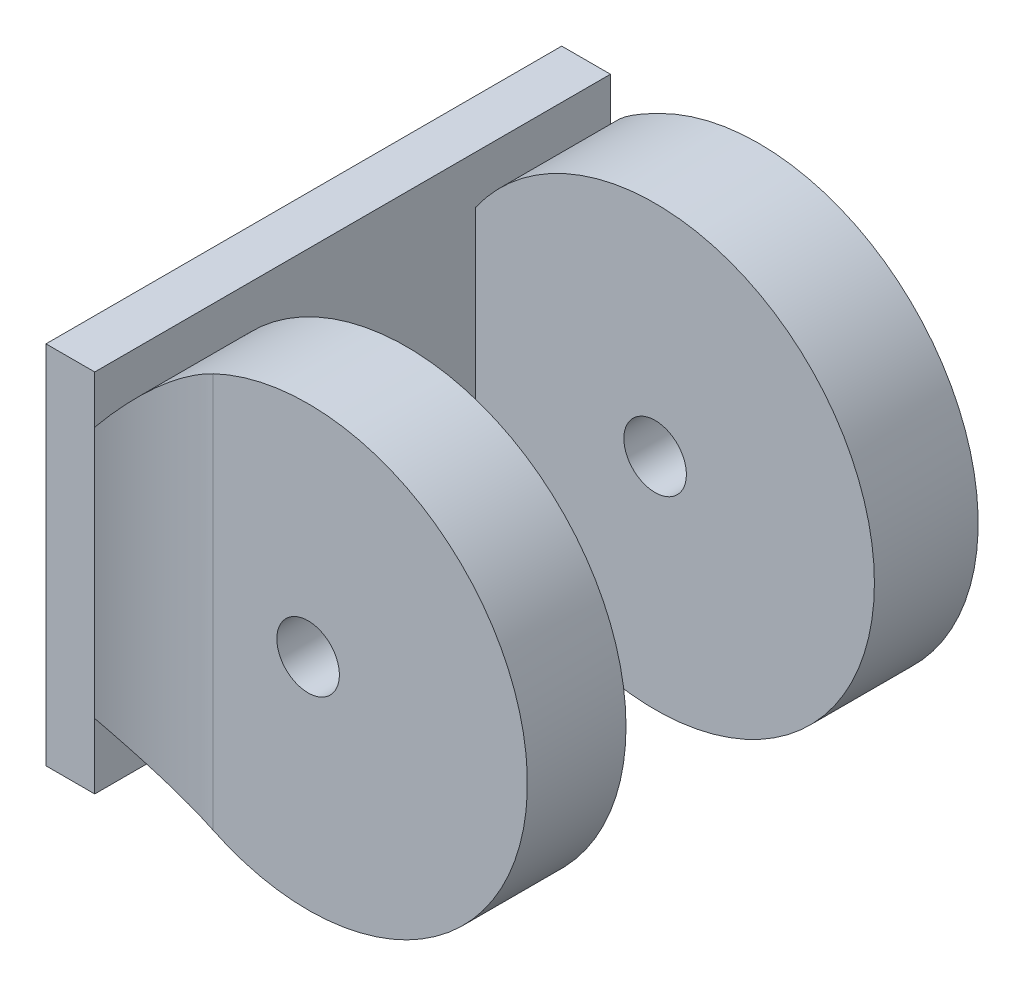
SolidWorks part; units mm, degrees
ref_plane "Front Plane" through (0, 0, 0) normal (0, 0, 1) x (1, 0, 0)
ref_plane "Top Plane" through (0, 0, 0) normal (0, 1, 0) x (1, 0, 0)
ref_plane "Right Plane" through (0, 0, 0) normal (1, 0, 0) x (0, 0, -1)
sketch "Sketch1" plane through (0, 0, 126.3564) normal (0, 0, -1) x (-1, 0, 0)
  circle A0 centre (-188.7243, 64.1657) radius 18
extrude "Boss-Extrude1" add sketch "Sketch1" along normal blind 9 and the other way blind 28
sketch "Sketch2" plane through (-6.9482, -29.4464, 0) normal (0.0708, 0.9975, 0) x (0.9975, -0.0708, 0)
  line L1 (217.5342, -125.8721) -> (167.5262, -125.8721)
  line L2 (217.5342, -125.8721) -> (217.5342, -146.2611)
  line L3 (217.5342, -146.2611) -> (167.5262, -146.2611)
  line L4 (167.5262, -125.8721) -> (167.5262, -146.2611)
extrude "Cut-Extrude1" cut sketch "Sketch2" along normal blind 137
sketch "Sketch6" plane through (0, 0, 117.3564) normal (0, 0, -1) x (-1, 0, 0)
  circle A0 centre (-188.7243, 64.1657) radius 2.5668
extrude "Cut-Extrude2" cut sketch "Sketch6" against normal blind 40
sketch "Sketch7" plane through (0, 0, 0) normal (1, 0, 0) x (0, 0, -1)
  line L1 (-157.1458, 78.4462) -> (-114.8145, 78.4462)
  line L2 (-157.1458, 78.4462) -> (-157.1458, 48.4462)
  line L3 (-157.1458, 48.4462) -> (-114.8145, 48.4462)
  line L4 (-114.8145, 78.4462) -> (-114.8145, 48.4462)
  dimension "D1" = 30
  dimension "D2" = 30
extrude "Boss-Extrude2" add sketch "Sketch7" along normal blind 4 from offset 170
fillet "Fillet1" radius 10 2 edges at (174, 64.1657, 154.3564) (174, 64.1657, 117.3564)
